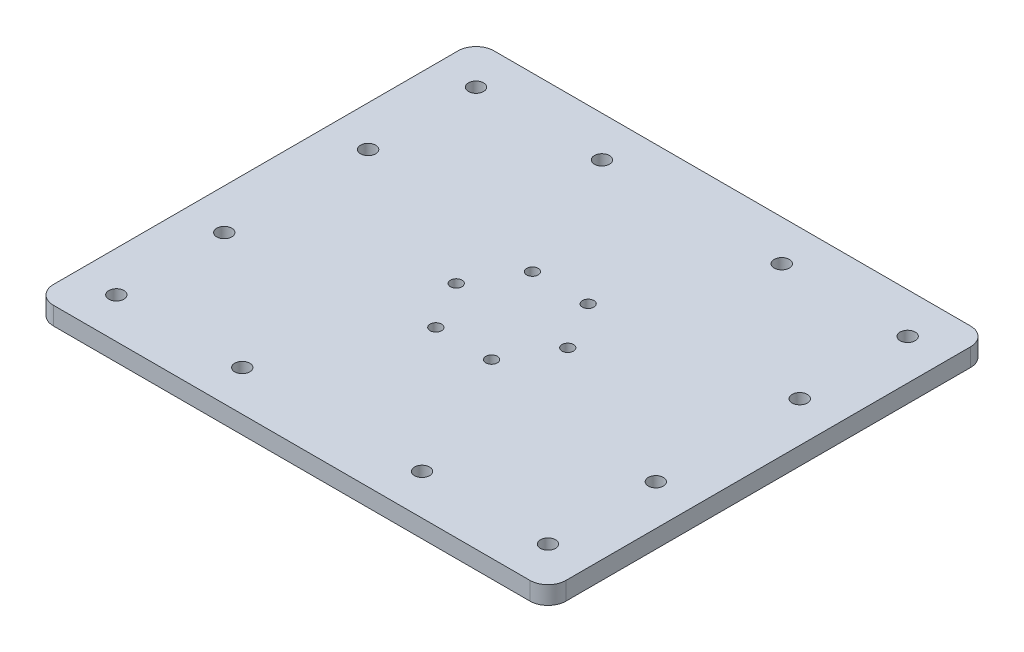
SolidWorks part; units mm, degrees
ref_plane "Front Plane" through (0, 0, 0) normal (0, 0, 1) x (1, 0, 0)
ref_plane "Top Plane" through (0, 0, 0) normal (0, 1, 0) x (1, 0, 0)
ref_plane "Right Plane" through (0, 0, 0) normal (1, 0, 0) x (0, 0, -1)
sketch "Sketch1" plane through (0, 0, 0) normal (0, 1, 0) x (1, 0, 0)
  line L0 (-120, 100) -> (-120, -100) construction
  line L1 (-132.5, 122.5) -> (132.5, 122.5)
  line L2 (-142.5, 112.5) -> (-142.5, -112.5)
  line L3 (-132.5, -122.5) -> (132.5, -122.5)
  line L4 (142.5, 112.5) -> (142.5, -112.5)
  line L5 (-142.5, 122.5) -> (142.5, -122.5) construction
  line L6 (-142.5, -122.5) -> (142.5, 122.5) construction
  line L7 (-120, -100) -> (120, -100) construction
  line L8 (120, 100) -> (120, -100) construction
  line L9 (-120, 100) -> (120, 100) construction
  line L10 (-142.5, -122.5) -> (142.5, -122.5) construction
  line L11 (-142.5, 122.5) -> (-142.5, -122.5) construction
  line L12 (142.5, 122.5) -> (142.5, -122.5) construction
  line L13 (-142.5, 122.5) -> (142.5, 122.5) construction
  line L14 (-120, 40) -> (120, 40) construction
  line L15 (120, -40) -> (-120, -40) construction
  line L16 (50, 100) -> (50, -100) construction
  line L17 (-50, 100) -> (-50, -100) construction
  line L18 (0, 0) -> (31, 0) construction
  arc A0 (-132.5, -122.5) -> (-142.5, -112.5) centre (-132.5, -112.5) cw
  arc A1 (132.5, -122.5) -> (142.5, -112.5) centre (132.5, -112.5) ccw
  arc A2 (142.5, 112.5) -> (132.5, 122.5) centre (132.5, 112.5) ccw
  arc A3 (-142.5, 112.5) -> (-132.5, 122.5) centre (-132.5, 112.5) cw
  circle A6 centre (120, 40) radius 4.2
  circle A7 centre (120, -40) radius 4.2
  circle A8 centre (-120, 40) radius 4.2
  circle A9 centre (-120, -40) radius 4.2
  circle A10 centre (-120, 100) radius 4.2
  circle A11 centre (-50, 100) radius 4.2
  circle A12 centre (50, 100) radius 4.2
  circle A13 centre (120, 100) radius 4.2
  circle A14 centre (120, -100) radius 4.2
  circle A15 centre (50, -100) radius 4.2
  circle A16 centre (-50, -100) radius 4.2
  circle A17 centre (-120, -100) radius 4.2
  circle A24 centre (31, 0) radius 3.2
  circle A25 centre (15.5, -26.8468) radius 3.2
  circle A26 centre (-15.5, -26.8468) radius 3.2
  circle A27 centre (-31, 0) radius 3.2
  circle A28 centre (-15.5, 26.8468) radius 3.2
  circle A29 centre (15.5, 26.8468) radius 3.2
  point P0 (0, 0)
  point P58 (0, 0)
  point P59 (0, 0)
  dimension "D4" = 10
  dimension "D5" = 6
  dimension "D1" = 285
  dimension "D2" = 245
  dimension "D6" = 31
  dimension "D3" = 22.5
base flange "Base-Flange1" sketch "Sketch1" thickness 10 reverse thickness direction no parameters "D1"=0.7366
sketch "Bend-Lines1" [suppressed] plane through (0, 0, 0) normal (0, 1, 0) x (1, 0, 0)
sketch "Bounding-Box1" [suppressed] plane through (0, 0, 0) normal (0, 1, 0) x (1, 0, 0)
sheet metal parameters "Sheet-Metal2" thickness 10 parameters "D1"=0.7366
flat pattern "Flat-Pattern2" [suppressed]
sketch "Bend-Lines2" plane through (0, 0, 0) normal (0, 1, 0) x (1, 0, 0)
sketch3d "Bounding-Box2" [suppressed]
  line L0 (-10, 235, 0) -> (275, 235, 0) construction
  line L1 (-10, -10, 0) -> (275, -10, 0) construction
  line L2 (-10, 235, 0) -> (-10, -10, 0) construction
  line L3 (275, 235, 0) -> (275, -10, 0) construction
